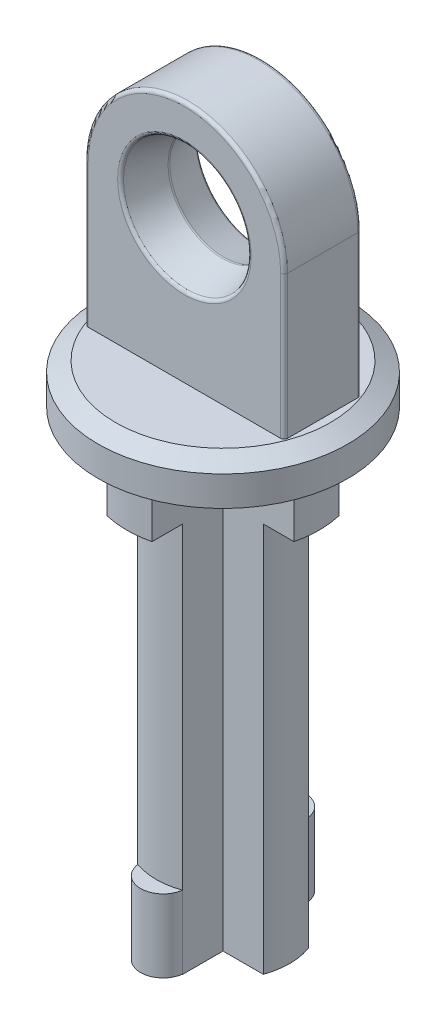
SolidWorks part; units mm, degrees
ref_plane "Alzado" through (0, 0, 0) normal (0, 0, 1) x (1, 0, 0)
ref_plane "Planta" through (0, 0, 0) normal (0, 1, 0) x (1, 0, 0)
ref_plane "Vista lateral" through (0, 0, 0) normal (1, 0, 0) x (0, 0, -1)
sketch "Croquis1" plane through (0, 0, 0) normal (0, 1, 0) x (1, 0, 0)
  circle A0 centre (0, 0) radius 5.5
  dimension "D1" = 11
extrude "Saliente-Extruir1" add sketch "Croquis1" along normal blind 26.5
sketch "Croquis2" plane through (0, 26.5, 0) normal (0, 1, 0) x (1, 0, 0)
  circle A0 centre (0, 0) radius 7.2
  dimension "D1" = 14.4
extrude "Saliente-Extruir2" add sketch "Croquis2" along normal blind 2.3
sketch "Croquis3" plane through (0, 28.8, 0) normal (0, 1, 0) x (1, 0, 0)
  line L0 (-5.75, 0) -> (0, 0) construction
  line L1 (-5.75, 2.225) -> (-5.75, -2.225)
  line L2 (-5.75, -2.225) -> (5.75, -2.225)
  line L3 (5.75, -2.225) -> (5.75, 2.225)
  line L4 (5.75, 2.225) -> (-5.75, 2.225)
  line L5 (0, 0) -> (5.75, 0) construction
  line L6 (0, 2.225) -> (0, 0) construction
  line L7 (0, 0) -> (0, -2.225) construction
  point P4 (0, 0)
  point P8 (-5.75, 0)
  dimension "D1" = 11.5
  dimension "D2" = 4.45
extrude "Saliente-Extruir3" add sketch "Croquis3" along normal blind 14
sketch "Croquis4" plane through (0, 0, 2.225) normal (0, 0, 1) x (1, 0, 0)
  line L0 (-5.75, 42.8) -> (5.75, 42.8)
  line L1 (5.75, 42.8) -> (5.75, 37.05)
  line L3 (-5.75, 42.8) -> (-5.75, 37.05)
  arc A1 (5.75, 37.05) -> (-5.75, 37.05) centre (0, 37.05) ccw
  line M6 (5.75, 28.8) -> (5.75, 42.8)
  line M7 (5.75, 42.8) -> (-5.75, 42.8)
  line M8 (-5.75, 42.8) -> (-5.75, 28.8)
extrude "Cortar-Extruir1" cut sketch "Croquis4" against normal blind 13.37 contours A1 M6 M7 | A1 L0 M8 | L0 L1 A1 L3 region at (4.4656, 41.5156, 2.225) region at (-4.4656, 41.5156, 2.225)
sketch "Croquis6" plane through (0, 0, 0) normal (0, -1, 0) x (1, 0, 0)
  circle A0 centre (0, 0) radius 4
  dimension "D1" = 8
extrude "Cortar-Extruir2" cut sketch "Croquis6" against normal up to surface (26.5 mm away) up to face at (0, 26.5, 5.5)
sketch "Croquis7" plane through (0, 0, 2.225) normal (0, 0, 1) x (1, 0, 0)
  circle A0 centre (0, 37.05) radius 2.8
  dimension "D1" = 5.6
extrude "Cortar-Extruir3" cut sketch "Croquis7" against normal blind 26.37
chamfer "Chaflán1" distance 0.9 angle 75 1 edges at (2.8, 37.05, 2.225) first distance on face at (2.8, 37.05, 2.225)
chamfer "Chaflán2" distance 0.9 angle 75 1 edges at (2.8, 37.05, -2.225) first distance on face at (2.8, 37.05, -2.225)
fillet "Redondeo1" radius 0.2 6 edges at (5.75, 32.925, 2.225) (0, 42.8, 2.225) (-5.75, 32.925, 2.225) (5.75, 32.925, -2.225) (-5.75, 32.925, -2.225) (0, 42.8, -2.225)
fillet "Redondeo2" radius 0.2 3 edges at (-3.7, 37.05, 2.225) (-3.1038, 37.05, 0) (3.7, 37.05, -2.225)
ref_plane "Plano2" through (0, 0, 12.225) normal (0, 0, 1) x (1, 0, 0)
sketch "Croquis11" plane through (0, 0, 12.225) normal (0, 0, 1) x (1, 0, 0)
  line L0 (-5.5, 26.5) -> (5.5, 26.5) construction
  line L1 (-2, 26.5) -> (2, 26.5)
  line L2 (-2, 26.5) -> (-2, 4.2)
  line L3 (-2, 4.2) -> (2, 4.2)
  line L4 (2, 26.5) -> (2, 4.2)
  line L5 (0, 4.2) -> (0, 0) construction
  dimension "D1" = 22.3
  dimension "D2" = 4
extrude "Cortar-Extruir4" cut sketch "Croquis11" against normal through all
sketch "Croquis13" plane through (0, 0, 0) normal (0, -1, 0) x (1, 0, 0)
  line L0 (-2, 5.1235) -> (-2, -5.1235) construction
  line L1 (2, 5.1235) -> (2, -5.1235) construction
  line L2 (-2, -4.1979) -> (4.5201, 1.0916)
  line L3 (2, 4.1979) -> (-4.5201, -1.0916)
  line L4 (-1.26, 1.5532) -> (1.26, -1.5532) construction
  line L5 (-2, -4.1979) -> (2, -4.1979) construction
  arc A0 (-4.5201, -1.0916) -> (-2, -4.1979) centre (0, 0) ccw
  arc A1 (4.5201, 1.0916) -> (2, 4.1979) centre (0, 0) ccw
  point P17 (0, 0)
  dimension "D1" = 9.3
extrude "Cortar-Extruir5" cut sketch "Croquis13" against normal blind 8.4
fillet "Redondeo3" radius 0.2 8 edges at (2, 4.2, 4.6607) (-2, 4.2, 4.2938) (2, 26.5, 4.2938) (-2, 26.5, 4.2938) (-2, 26.5, -4.2938) (2, 26.5, -4.2938) (2, 4.2, -4.2938) (-2, 4.2, -4.6607)
ref_plane "Plano3" through (15.75, 0, 0) normal (1, 0, 0) x (0, 0, -1)
sketch "Croquis14" plane through (15.75, 0, 0) normal (1, 0, 0) x (0, 0, -1)
  line L0 (-7.2, 26.5) -> (7.2, 26.5)
  line L1 (7.2, 26.5) -> (7.2, 0)
  line L2 (7.2, 0) -> (-7.2, 0)
  line L3 (-7.2, 0) -> (-7.2, 26.5)
extrude "Cortar-Extruir6" cut sketch "Croquis14" against normal blind 28.4
sketch "Croquis15" plane through (0, 26.5, 0) normal (0, -1, 0) x (1, 0, 0)
  line L0 (-1.3, 5.3956) -> (-1.3, 1.3)
  line L1 (-1.3, 1.3) -> (-5.3956, 1.3)
  line L2 (5.3956, 1.3) -> (1.3, 1.3)
  line L3 (1.3, 1.3) -> (1.3, 5.3956)
  line L4 (1.3, -5.3956) -> (1.3, -1.3)
  line L5 (1.3, -1.3) -> (5.3956, -1.3)
  line L6 (-5.3956, -1.3) -> (-1.3, -1.3)
  line L7 (-1.3, -1.3) -> (-1.3, -5.3956)
  arc A0 (-5.3956, 1.3) -> (-5.3956, -1.3) centre (0, 0) ccw
  arc A1 (-1.3, -5.3956) -> (1.3, -5.3956) centre (0, 0) ccw
  arc A2 (5.3956, -1.3) -> (5.3956, 1.3) centre (0, 0) ccw
  arc A3 (1.3, 5.3956) -> (-1.3, 5.3956) centre (0, 0) ccw
  point P18 (0, 0)
  dimension "D1" = 11.1
  dimension "D2" = 4
  dimension "D3" = 2.6
extrude "Saliente-Extruir4" add sketch "Croquis15" along normal blind 3.4 separate body
sketch "Croquis16" plane through (0, 23.1, 0) normal (0, -1, 0) x (1, 0, 0)
  line L0 (-3.6239, 1.3) -> (-1.3, 1.3)
  line L2 (-1.3, 1.3) -> (-1.3, 3.6239)
  line L3 (-1.3, 5.3956) -> (-1.3, 1.3) construction
  line L4 (-3.6239, -1.3) -> (-1.3, -1.3)
  line L5 (-1.3, -1.3) -> (-1.3, -3.6239)
  line L6 (-1.3, -1.3) -> (-1.3, -5.3956) construction
  line L7 (1.3, -3.6239) -> (1.3, -1.3)
  line L9 (1.3, -1.3) -> (3.6239, -1.3)
  line L10 (1.3, -1.3) -> (5.3956, -1.3) construction
  line L11 (1.3, 3.6239) -> (1.3, 1.3)
  line L12 (1.3, 1.3) -> (1.3, 5.3956) construction
  line L13 (1.3, 1.3) -> (3.6239, 1.3)
  arc A0 (-3.6239, 1.3) -> (-3.6239, -1.3) centre (0, 0) ccw
  arc A1 (1.3, 3.6239) -> (-1.3, 3.6239) centre (0, 0) ccw
  arc A2 (3.6239, -1.3) -> (3.6239, 1.3) centre (0, 0) ccw
  arc A3 (-1.3, -3.6239) -> (1.3, -3.6239) centre (0, 0) ccw
  dimension "D1" = 7.7
extrude "Saliente-Extruir5" add sketch "Croquis16" along normal blind 22.5
sketch "Croquis17" plane through (0, 0.6, 0) normal (0, -1, 0) x (1, 0, 0)
  line L0 (-3.45, 0) -> (3.45, 0) construction
  line L1 (-3.45, 1.3) -> (3.45, 1.3)
  line L2 (-3.45, -1.3) -> (3.45, -1.3)
  line L3 (-4.75, 0) -> (-4.75, -1.3) construction
  line L4 (-5.3956, -1.3) -> (-1.3, -1.3) construction
  line L5 (4.75, 0) -> (4.75, -1.3) construction
  line L6 (1.3, -1.3) -> (5.3956, -1.3) construction
  arc A2 (-3.45, 1.3) -> (-3.45, -1.3) centre (-3.45, 0) ccw
  arc A3 (3.45, -1.3) -> (3.45, 1.3) centre (3.45, 0) ccw
  point P8 (0, 0)
  dimension "D1" = 9.5
extrude "Saliente-Extruir6" add sketch "Croquis17" against normal blind 4.2
chamfer "Chaflán3" distance 1 angle 30 1 edges at (0, 28.8, 7.2) first distance on face at (0, 28.8, 0)
combine bodies "Combinar1" operation type add bodies to combine 113 114
combine bodies "Combinar2" operation type add bodies to combine 112 115
move or copy body "Sólido-Mover/Copiar1" bodies to move or copy 116 copy no rotation origin (0, 0, 0) rotation axis (0, 1, 0) rotation angle 90
combine bodies "Combinar3" operation type add bodies to combine 117 111
